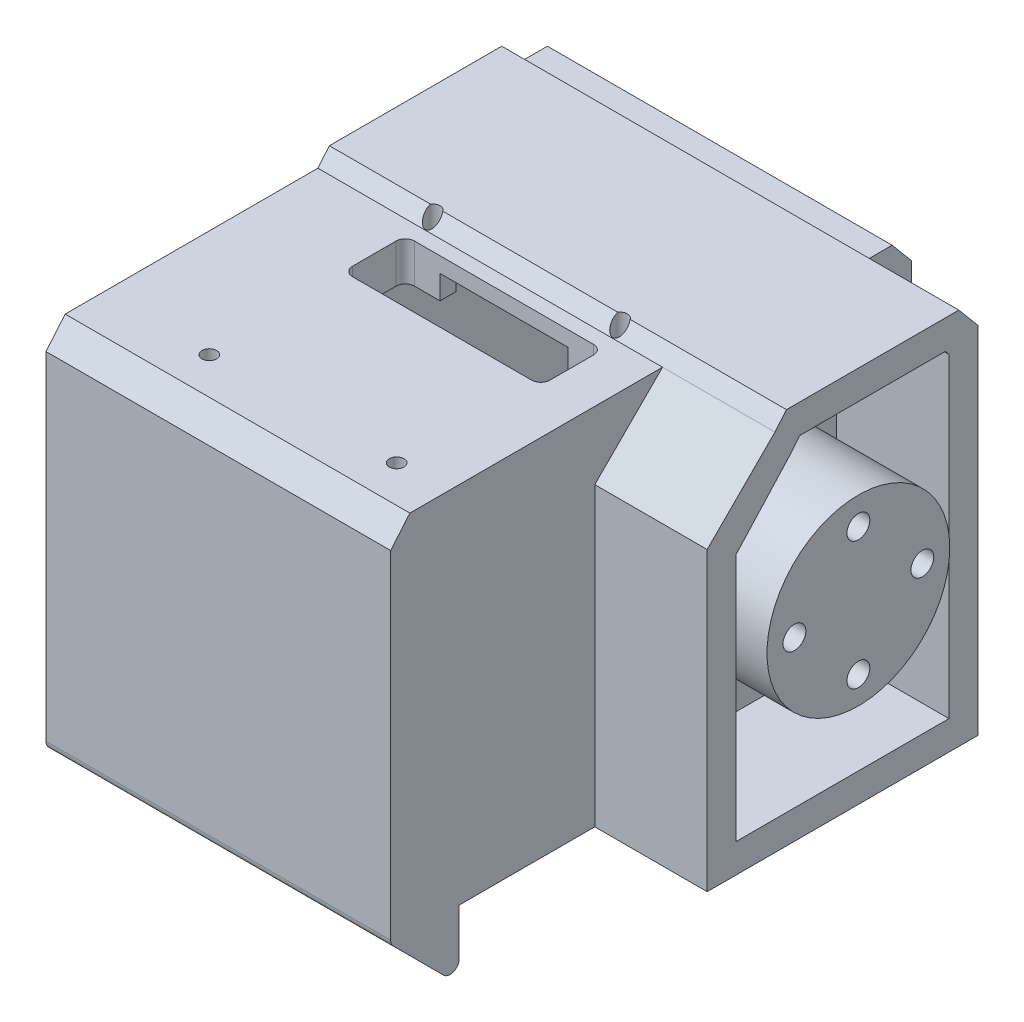
SolidWorks part; units mm, degrees
material "PLA"
ref_plane "Front Plane" through (0, 0, 0) normal (0, 0, 1) x (1, 0, 0)
ref_plane "Top Plane" through (0, 0, 0) normal (0, 1, 0) x (1, 0, 0)
ref_plane "Right Plane" through (0, 0, 0) normal (1, 0, 0) x (0, 0, -1)
sketch "Sketch1" plane through (0, 0, 0) normal (1, 0, 0) x (0, 0, -1)
  line L0 (-25.985, 0) -> (25.985, 0) construction
  line L1 (0, 21.625) -> (0, -21.625) construction
  line L7 (-25.985, -21.625) -> (25.985, -21.625)
  line L8 (-25.985, -21.625) -> (-25.985, 21.625)
  line L9 (-25.985, 21.625) -> (25.985, 21.625)
  line L10 (25.985, -21.625) -> (25.985, 21.625)
  point P5 (0, 0)
  dimension "D1" = 51.97
  dimension "D2" = 43.25
extrude "Boss-Extrude1" add sketch "Sketch1" along normal blind 3.175
sketch "Sketch2" plane through (3.175, 0, 0) normal (1, 0, 0) x (0, 0, -1)
  line L8 (-22.81, 18.45) -> (-22.81, -18.45)
  line L9 (-22.81, -18.45) -> (22.81, -18.45)
  line L10 (22.81, -18.45) -> (22.81, 18.45)
  line L11 (22.81, 18.45) -> (-22.81, 18.45)
  line L12 (-22.81, 18.45) -> (-22.81, -18.45)
  line L13 (-22.81, -18.45) -> (22.81, -18.45)
  line L14 (22.81, -18.45) -> (22.81, 18.45)
  line L15 (22.81, 18.45) -> (-22.81, 18.45)
  line L16 (-25.985, 21.625) -> (-25.985, -21.625)
  line L17 (-25.985, -21.625) -> (25.985, -21.625)
  line L18 (25.985, -21.625) -> (25.985, 21.625)
  line L19 (25.985, 21.625) -> (-25.985, 21.625)
  line L20 (-25.985, 21.625) -> (-25.985, -21.625)
  line L21 (-25.985, -21.625) -> (25.985, -21.625)
  line L22 (25.985, -21.625) -> (25.985, 21.625)
  line L23 (25.985, 21.625) -> (-25.985, 21.625)
  dimension "D1" = 3.175
  dimension "D2" = 0
extrude "Boss-Extrude2" add sketch "Sketch2" along normal blind 25.12
sketch "Sketch5" plane through (0, 18.45, 0) normal (0, -1, 0) x (1, 0, 0)
  line L0 (6.0285, -6.9385) -> (3.175, -6.9385)
  line L1 (25.4415, -6.9385) -> (28.295, -6.9385)
  line L4 (3.175, 22.81) -> (3.175, -22.81)
  line L5 (3.175, -22.81) -> (28.295, -22.81)
  line L6 (28.295, -22.81) -> (28.295, 22.81)
  line L7 (28.295, 22.81) -> (3.175, 22.81)
  line L8 (3.175, 22.81) -> (3.175, -6.9385)
  line L10 (28.295, -6.9385) -> (28.295, 22.81)
  line L11 (28.295, 22.81) -> (3.175, 22.81)
  line L36 (26.535, -2.15) -> (22.735, -2.15)
  line L37 (26.535, 4.625) -> (26.535, -2.15)
  line L38 (25.038, 4.625) -> (26.535, 4.625)
  line L39 (25.1773, 4.8479) -> (25.038, 4.625)
  line L40 (25.1773, 15.8031) -> (25.1773, 4.8479)
  line L41 (7.4927, 17.0031) -> (23.9773, 17.0031)
  line L42 (6.2927, 4.8479) -> (6.2927, 15.8031)
  line L43 (6.432, 4.625) -> (6.2927, 4.8479)
  line L44 (4.935, 4.625) -> (6.432, 4.625)
  line L45 (4.935, -2.15) -> (4.935, 4.625)
  line L46 (8.735, -2.15) -> (4.935, -2.15)
  line L47 (8.735, -3.9136) -> (8.735, -2.15)
  line L48 (4.375, -6.9385) -> (6.0285, -6.9385)
  line L49 (3.875, 20.2102) -> (3.875, -6.4385)
  line L50 (26.0951, 21.71) -> (5.3746, 21.71)
  line L51 (27.595, -6.4385) -> (27.595, 20.2105)
  line L52 (25.4415, -6.9385) -> (27.095, -6.9385)
  line L53 (22.735, -2.15) -> (22.735, -3.9136)
  line L54 (26.535, -2.15) -> (22.735, -2.15)
  line L55 (26.535, 4.625) -> (26.535, -2.15)
  line L56 (25.038, 4.625) -> (26.535, 4.625)
  line L57 (25.1773, 4.8479) -> (25.038, 4.625)
  line L58 (25.1773, 15.8031) -> (25.1773, 4.8479)
  line L59 (7.4927, 17.0031) -> (23.9773, 17.0031)
  line L60 (6.2927, 4.8479) -> (6.2927, 15.8031)
  line L61 (6.432, 4.625) -> (6.2927, 4.8479)
  line L62 (4.935, 4.625) -> (6.432, 4.625)
  line L63 (4.935, -2.15) -> (4.935, 4.625)
  line L64 (8.735, -2.15) -> (4.935, -2.15)
  line L65 (8.735, -3.9136) -> (8.735, -2.15)
  line L71 (22.735, -2.15) -> (22.735, -3.9136)
  arc A12 (25.1773, 15.8031) -> (23.9773, 17.0031) centre (23.9773, 15.8031) ccw
  arc A13 (7.4927, 17.0031) -> (6.2927, 15.8031) centre (7.4927, 15.8031) ccw
  arc A14 (8.735, -3.9136) -> (6.0285, -6.9385) centre (15.735, -12.9) ccw
  arc A15 (3.875, -6.4385) -> (4.375, -6.9385) centre (4.375, -6.4385) ccw
  arc A16 (27.095, -6.9385) -> (27.595, -6.4385) centre (27.095, -6.4385) ccw
  arc A17 (25.4415, -6.9385) -> (22.735, -3.9136) centre (15.735, -12.9) ccw
  arc A18 (25.1773, 15.8031) -> (23.9773, 17.0031) centre (23.9773, 15.8031) ccw
  arc A19 (7.4927, 17.0031) -> (6.2927, 15.8031) centre (7.4927, 15.8031) ccw
  arc A20 (8.735, -3.9136) -> (6.0285, -6.9385) centre (15.735, -12.9) ccw
  arc A23 (25.4415, -6.9385) -> (22.735, -3.9136) centre (15.735, -12.9) ccw
  circle A68 centre (5.485, -4.6) radius 0.8
  circle A69 centre (5.485, 19.85) radius 0.8
  circle A70 centre (25.985, 19.85) radius 0.8
  circle A71 centre (25.985, -4.6) radius 0.8
  spline S4 degree 3 poles (199.8506, -959.1962) (36.727, -55.2614) (14.0519, 23.473) (4.9866, 21.6619) (4.8913, 21.6332) (4.7098, 21.558) (4.6238, 21.5118) (4.4608, 21.403) (4.3836, 21.3399) (4.1763, 21.1325) (4.0645, 20.9654) (1.0086, 13.5957) (53.0588, -19.6485) (521.6785, 875.7094) knots -11.579327 -11.579327 -11.579327 -11.579327 0.125 0.125 0.25 0.25 0.375 0.375 0.5 0.5 0.75 0.75 10.719736 10.719736 10.719736 10.719736 only from (5.3746, 21.71) to (3.875, 20.2102)
  spline S5 degree 3 poles (-953.307, -174.2909) (-49.38, -11.1451) (29.3583, 11.5329) (27.5469, 20.5985) (27.5181, 20.6937) (27.443, 20.8752) (27.3968, 20.9612) (27.288, 21.1242) (27.2248, 21.2014) (27.0175, 21.4088) (26.8503, 21.5206) (19.4805, 24.5762) (-13.7629, -27.4761) (881.6326, -496.0119) knots -11.579675 -11.579675 -11.579675 -11.579675 0.125 0.125 0.25 0.25 0.375 0.375 0.5 0.5 0.75 0.75 10.719832 10.719832 10.719832 10.719832 only from (27.595, 20.2105) to (26.0951, 21.71)
  dimension "D3" = 1.6
  dimension "D1" = 0.2
  dimension "D2" = 0
extrude "Boss-Extrude4" add sketch "Sketch5" along normal blind 2.6
sketch "Sketch6" plane through (0, 18.45, 0) normal (0, -1, 0) x (1, 0, 0)
  line L1 (4.935, 4.625) -> (26.535, 4.625)
  line L2 (4.935, 4.625) -> (4.935, -2.15)
  line L3 (4.935, -2.15) -> (26.535, -2.15)
  line L4 (26.535, 4.625) -> (26.535, -2.15)
  line L18 (6.0285, -6.9385) -> (3.175, -6.9385)
  line L19 (3.175, -6.9385) -> (3.175, -22.81)
  line L20 (3.175, -22.81) -> (28.295, -22.81)
  line L21 (28.295, -22.81) -> (28.295, -6.9385)
  line L22 (28.295, -6.9385) -> (25.4415, -6.9385)
  line L23 (22.735, -3.9136) -> (22.735, -2.15)
  line L24 (22.735, -2.15) -> (26.535, -2.15)
  line L25 (26.535, -2.15) -> (26.535, 4.625)
  line L26 (26.535, 4.625) -> (25.038, 4.625)
  line L27 (25.038, 4.625) -> (25.1773, 4.8479)
  line L28 (25.1773, 4.8479) -> (25.1773, 15.8031)
  line L29 (23.9773, 17.0031) -> (7.4927, 17.0031)
  line L30 (6.2927, 15.8031) -> (6.2927, 4.8479)
  line L31 (6.2927, 4.8479) -> (6.432, 4.625)
  line L32 (6.432, 4.625) -> (4.935, 4.625)
  line L33 (4.935, 4.625) -> (4.935, -2.15)
  line L34 (4.935, -2.15) -> (8.735, -2.15)
  line L35 (8.735, -2.15) -> (8.735, -3.9136)
  line L42 (22.735, -2.15) -> (26.535, -2.15)
  line L43 (26.535, -2.15) -> (26.535, 4.625)
  line L44 (26.535, 4.625) -> (25.038, 4.625)
  line L50 (6.432, 4.625) -> (4.935, 4.625)
  line L51 (4.935, 4.625) -> (4.935, -2.15)
  line L52 (4.935, -2.15) -> (8.735, -2.15)
  arc A4 (8.735, -3.9136) -> (6.0285, -6.9385) centre (15.735, -12.9) ccw
  arc A5 (25.4415, -6.9385) -> (22.735, -3.9136) centre (15.735, -12.9) ccw
  arc A6 (25.1773, 15.8031) -> (23.9773, 17.0031) centre (23.9773, 15.8031) ccw
  arc A7 (7.4927, 17.0031) -> (6.2927, 15.8031) centre (7.4927, 15.8031) ccw
  line M35 (22.735, -2.15) -> (26.535, -2.15)
  line M36 (26.535, -2.15) -> (26.535, 4.625)
  line M37 (26.535, 4.625) -> (25.038, 4.625)
  line M45 (6.432, 4.625) -> (4.935, 4.625)
  line M46 (4.935, 4.625) -> (4.935, -2.15)
  line M47 (4.935, -2.15) -> (8.735, -2.15)
  dimension "D1" = 0
extrude "Cut-Extrude2" cut sketch "Sketch6" against normal through all contours L3 L1 M47 M35 M36 M37 M45 M46 region at (15.735, 18.45, 1.2375)
fillet "Fillet4" radius 1 4 edges at (26.535, 18.7375, -2.15) (26.535, 18.7375, 4.625) (4.935, 18.7375, -2.15) (4.935, 18.7375, 4.625)
sketch "Sketch7" plane through (0, 21.625, 0) normal (0, 1, 0) x (1, 0, 0)
  line L0 (28.295, 25.985) -> (28.295, -25.985) construction
  line L1 (0, -25.985) -> (28.295, -25.985)
  line L2 (0, -25.985) -> (0, 3.765)
  line L3 (0, 3.765) -> (28.295, 3.765)
  line L4 (28.295, -25.985) -> (28.295, 3.765)
  line M5 (25.535, -4.625) -> (5.935, -4.625)
  arc M6 (5.935, -4.625) -> (4.935, -3.625) centre (5.935, -3.625) cw
  line M7 (4.935, -3.625) -> (4.935, 1.15)
  arc M8 (4.935, 1.15) -> (5.935, 2.15) centre (5.935, 1.15) cw
  line M9 (5.935, 2.15) -> (25.535, 2.15)
  arc M10 (25.535, 2.15) -> (26.535, 1.15) centre (25.535, 1.15) cw
  line M11 (26.535, 1.15) -> (26.535, -3.625)
  arc M12 (26.535, -3.625) -> (25.535, -4.625) centre (25.535, -3.625) cw
  line M13 (0, 25.985) -> (0, -25.985)
  line M14 (0, -25.985) -> (28.295, -25.985)
  line M15 (28.295, -25.985) -> (28.295, 25.985)
  dimension "D1" = 29.75
extrude "Cut-Extrude3" cut sketch "Sketch7" against normal blind 1.5 contours L3 M13 M14 M15 M12 M5 M6 M7 M8 M9 M10 M11 region at (13.8158, 21.625, 13.1727)
chamfer "Chamfer3" distance 1.5 angle 40 1 edges at (14.1475, 21.625, -3.765) first distance on face at (14.1475, 20.875, -3.765)
chamfer "Chamfer4" distance 2.5 angle 40 1 edges at (14.1475, 20.125, 25.985) first distance on face at (14.1475, -0.75, 25.985)
chamfer "Chamfer5" distance 2.5 angle 40 1 edges at (14.1475, 21.625, -25.985) first distance on face at (14.1475, 0, -25.985)
sketch "Sketch8" plane through (0, -18.45, 0) normal (0, 1, 0) x (1, 0, 0)
  line L1 (8.535, 2.2774) -> (8.535, -21.2062)
  line L6 (22.935, -21.2062) -> (22.935, 2.2774)
  line L8 (5.6661, 6.9407) -> (3.175, 6.9407)
  line L11 (25.803, 6.9392) -> (28.295, 6.9392)
  line L16 (8.8158, -21.9777) -> (8.8158, -22.81)
  line L18 (22.6542, -21.9776) -> (22.6542, -22.81)
  line L19 (3.175, 22.81) -> (3.175, -22.81)
  line L20 (3.175, -22.81) -> (28.295, -22.81)
  line L21 (28.295, -22.81) -> (28.295, 22.81)
  line L22 (28.295, 22.81) -> (3.175, 22.81)
  line L23 (3.175, 6.9407) -> (3.175, -22.81)
  line L24 (3.175, -22.81) -> (8.8158, -22.81)
  line L25 (28.295, -22.81) -> (28.295, 6.9392)
  line L27 (22.6542, -22.81) -> (28.295, -22.81)
  arc A6 (5.6661, 6.9407) -> (9.0755, 3.2799) centre (15.735, 12.9) ccw
  arc A9 (9.0755, 3.2799) -> (8.535, 2.2774) centre (9.735, 2.2774) ccw
  arc A20 (8.535, -21.2062) -> (8.8158, -21.9777) centre (9.735, -21.2062) ccw
  arc A23 (22.6542, -21.9776) -> (22.935, -21.2062) centre (21.735, -21.2062) ccw
  arc A28 (22.935, 2.2774) -> (22.3945, 3.2799) centre (21.735, 2.2774) ccw
  arc A35 (22.3945, 3.2799) -> (25.803, 6.9392) centre (15.735, 12.9) ccw
  circle A56 centre (25.985, -16.1) radius 0.8
  circle A57 centre (5.485, 4.6) radius 0.8
  circle A58 centre (25.985, 4.6) radius 0.8
  circle A59 centre (5.485, -16.1) radius 0.8
  spline S5 degree 3 poles (5.6659, 6.9385) (5.666, 6.9385) (5.6664, 6.9383) (5.6671, 6.938) (5.6678, 6.9375) (5.6681, 6.9373) (5.6683, 6.9372) knots 0.329528 0.329528 0.329528 0.329528 0.414347 0.499166 0.583985 0.668804 0.668804 0.668804 0.668804
  line M1 (3.175, 22.81) -> (3.175, -22.81)
  line M2 (3.175, -22.81) -> (28.295, -22.81)
  line M3 (28.295, -22.81) -> (28.295, 22.81)
  dimension "D1" = 1.6
  dimension "D2" = 1.6
  dimension "D3" = 1.6
  dimension "D4" = 1.6
  dimension "D5" = 0
extrude "Boss-Extrude5" add sketch "Sketch8" along normal blind 1.9 contours A20 L1 A9 A6 L8 L16 A59 A57 M1 M2 | A35 A28 L6 A23 L18 L11 A58 A56 M2 M3 region at (5.8173, -18.45, 8.4819) region at (25.6526, -18.45, 8.4823)
sketch "Sketch9" plane through (0, 18.45, 0) normal (0, -1, 0) x (1, 0, 0)
  circle A0 centre (5.485, -4.6) radius 0.8 construction
  circle A1 centre (25.985, -4.6) radius 0.8 construction
  circle A2 centre (25.985, 19.85) radius 0.8 construction
  circle A3 centre (5.485, 19.85) radius 0.8 construction
  circle A4 centre (5.485, -4.6) radius 0.8
  circle A5 centre (25.985, -4.6) radius 0.8
  circle A6 centre (25.985, 19.85) radius 0.8
  circle A7 centre (5.485, 19.85) radius 0.8
extrude "Cut-Extrude4" cut sketch "Sketch9" against normal through all
sketch "Sketch10" plane through (0, -21.625, 0) normal (0, -1, 0) x (1, 0, 0)
  line L0 (28.295, 25.985) -> (28.295, -25.985) construction
  line L1 (0, 25.985) -> (28.295, 25.985)
  line L2 (0, 25.985) -> (0, -6.935)
  line L3 (0, -6.935) -> (28.295, -6.935)
  line L4 (28.295, 25.985) -> (28.295, -6.935)
  dimension "D1" = 32.92
extrude "Cut-Extrude5" cut sketch "Sketch10" against normal blind 1.9
chamfer "Chamfer6" distance 1.9 angle 40 1 edges at (14.1475, -19.725, -6.935) first distance on face at (14.1475, -20.675, -6.935)
sketch "Sketch11" plane through (0, -18.45, 0) normal (0, 1, 0) x (1, 0, 0)
  line L10 (3.175, 22.81) -> (3.175, 6.9407)
  line L11 (3.175, 6.9407) -> (5.6661, 6.9407)
  line L12 (8.535, 2.2774) -> (8.535, -21.2062)
  line L13 (8.8158, -21.9777) -> (8.8158, -22.81)
  line L14 (8.8158, -22.81) -> (22.6542, -22.81)
  line L15 (22.6542, -22.81) -> (22.6542, -21.9776)
  line L16 (22.935, -21.2062) -> (22.935, 2.2774)
  line L17 (25.803, 6.9392) -> (28.295, 6.9392)
  line L18 (28.295, 6.9392) -> (28.295, 22.81)
  line L19 (28.295, 22.81) -> (3.175, 22.81)
  line L20 (3.175, 22.81) -> (3.175, 6.9407)
  line L21 (3.175, 6.9407) -> (5.6661, 6.9407)
  line L27 (25.803, 6.9392) -> (28.295, 6.9392)
  line L28 (28.295, 6.9392) -> (28.295, 22.81)
  line L29 (28.295, 22.81) -> (3.175, 22.81)
  arc A0 (9.0755, 3.2799) -> (22.3945, 3.2799) centre (15.735, 9.9394) ccw
  arc A6 (5.6661, 6.9407) -> (9.0755, 3.2799) centre (15.735, 12.9) ccw
  arc A7 (9.0755, 3.2799) -> (8.535, 2.2774) centre (9.735, 2.2774) ccw
  arc A8 (8.535, -21.2062) -> (8.8158, -21.9777) centre (9.735, -21.2062) ccw
  arc A9 (22.6542, -21.9776) -> (22.935, -21.2062) centre (21.735, -21.2062) ccw
  arc A10 (22.935, 2.2774) -> (22.3945, 3.2799) centre (21.735, 2.2774) ccw
  arc A11 (22.3945, 3.2799) -> (25.803, 6.9392) centre (15.735, 12.9) ccw
  arc A12 (5.6661, 6.9407) -> (9.0755, 3.2799) centre (15.735, 12.9) ccw
  arc A17 (22.3945, 3.2799) -> (25.803, 6.9392) centre (15.735, 12.9) ccw
  dimension "D1" = 0
extrude "Cut-Extrude6" cut sketch "Sketch11" against normal through all
sketch "Sketch12" plane through (0, -18.45, 0) normal (0, 1, 0) x (1, 0, 0)
  circle A0 centre (25.985, 4.6) radius 0.8 construction
  circle A1 centre (25.985, -16.1) radius 0.8 construction
  circle A2 centre (5.485, -16.1) radius 0.8 construction
  circle A3 centre (5.485, 4.6) radius 0.8 construction
  circle A4 centre (25.985, 4.6) radius 0.8
  circle A5 centre (25.985, -16.1) radius 0.8
  circle A6 centre (5.485, -16.1) radius 0.8
  circle A7 centre (5.485, 4.6) radius 0.8
extrude "Cut-Extrude7" cut sketch "Sketch12" against normal through all
sketch "Sketch13" plane through (0, -21.625, 0) normal (0, -1, 0) x (1, 0, 0)
  line L0 (28.295, -5.3407) -> (28.295, 25.985) construction
  line L1 (0, -25.985) -> (28.295, -25.985)
  line L2 (0, -25.985) -> (0, 7.0246)
  line L3 (0, 7.0246) -> (28.295, 7.0246)
  line L4 (28.295, -25.985) -> (28.295, 7.0246)
extrude "Cut-Extrude8" cut sketch "Sketch13" against normal up to surface (1.9 mm away) up to face at (15.2058, -19.725, 0.7228)
sketch "Sketch14" plane through (28.295, 0, 0) normal (1, 0, 0) x (0, 0, -1)
  line L0 (6.9392, -16.55) -> (22.81, -16.55)
  line L1 (6.9392, -19.725) -> (22.81, -19.725)
  line L3 (6.9392, -16.55) -> (22.81, -16.55)
  line L5 (6.9392, -19.725) -> (22.81, -19.725)
  line L16 (-25.985, -19.725) -> (6.9392, -19.725)
  line L17 (6.9392, -19.725) -> (6.9392, -16.55)
  line L18 (6.9392, -16.55) -> (-22.81, -16.55)
  line L19 (-22.81, -16.55) -> (-22.81, 15.85)
  line L20 (-22.81, 15.85) -> (6.9385, 15.85)
  line L21 (6.9385, 15.85) -> (6.9385, 18.45)
  line L22 (6.9385, 18.45) -> (22.81, 18.45)
  line L23 (22.81, 18.45) -> (22.81, -19.725)
  line L24 (22.81, -19.725) -> (25.985, -19.725)
  line L25 (25.985, -19.725) -> (25.985, 19.125)
  line L26 (25.985, 19.125) -> (23.8873, 21.625)
  line L27 (23.8873, 21.625) -> (5.0236, 21.625)
  line L28 (5.0236, 21.625) -> (3.765, 20.125)
  line L29 (3.765, 20.125) -> (-23.8873, 20.125)
  line L30 (-23.8873, 20.125) -> (-25.985, 17.625)
  line L31 (-25.985, 17.625) -> (-25.985, -19.725)
  line L32 (-25.985, -19.725) -> (6.9392, -19.725)
  line L34 (6.9392, -16.55) -> (-22.81, -16.55)
  line L35 (-22.81, -16.55) -> (-22.81, 15.85)
  line L36 (-22.81, 15.85) -> (6.9385, 15.85)
  line L37 (6.9385, 15.85) -> (6.9385, 18.45)
  line L38 (6.9385, 18.45) -> (22.81, 18.45)
  line L39 (22.81, 18.45) -> (22.81, -16.55)
  line L40 (22.81, -19.725) -> (25.985, -19.725)
  line L41 (25.985, -19.725) -> (25.985, 19.125)
  line L42 (25.985, 19.125) -> (23.8873, 21.625)
  line L43 (23.8873, 21.625) -> (5.0236, 21.625)
  line L44 (5.0236, 21.625) -> (3.765, 20.125)
  line L45 (3.765, 20.125) -> (-23.8873, 20.125)
  line L46 (-23.8873, 20.125) -> (-25.985, 17.625)
  line L47 (-25.985, 17.625) -> (-25.985, -19.725)
  line M21 (-25.985, -19.725) -> (6.9392, -19.725)
  line M22 (6.9392, -19.725) -> (6.9392, -16.55)
  line M23 (6.9392, -16.55) -> (-22.81, -16.55)
  line M24 (-22.81, -16.55) -> (-22.81, 15.85)
  line M25 (-22.81, 15.85) -> (6.9385, 15.85)
  line M26 (6.9385, 15.85) -> (6.9385, 18.45)
  line M27 (6.9385, 18.45) -> (22.81, 18.45)
  line M28 (22.81, 18.45) -> (22.81, -19.725)
  line M29 (22.81, -19.725) -> (25.985, -19.725)
  line M30 (25.985, -19.725) -> (25.985, 19.125)
  line M31 (25.985, 19.125) -> (23.8873, 21.625)
  line M32 (23.8873, 21.625) -> (5.0236, 21.625)
  line M33 (5.0236, 21.625) -> (3.765, 20.125)
  line M34 (3.765, 20.125) -> (-23.8873, 20.125)
  line M35 (-23.8873, 20.125) -> (-25.985, 17.625)
  line M36 (-25.985, 17.625) -> (-25.985, -19.725)
  dimension "D1" = 0
extrude "Boss-Extrude6" add sketch "Sketch14" along normal blind 3.175 contours M36 M21 M22 M23 M24 M25 M26 M27 M28 M29 M30 M31 M32 M33 M34 M35 | L1 L0 M22 M28 | L40 L41 L42 L43 L44 L45 L46 L47 L32 L1 region at (28.295, -18.1375, -14.8746) region at (28.295, -18.1375, -6.275)
sketch "Sketch15" plane through (31.47, 0, 0) normal (1, 0, 0) x (0, 0, -1)
  line L0 (25.985, 0) -> (12.495, 0) construction
  line L1 (25.985, -19.725) -> (25.985, 19.125) construction
  circle A0 centre (12.495, 0) radius 10
  circle A1 centre (12.495, 0) radius 7 construction
  circle A2 centre (12.495, 7) radius 1.25
  circle A3 centre (19.495, 0) radius 1.25
  circle A4 centre (5.495, 0) radius 1.25
  circle A5 centre (12.495, -7) radius 1.25
  dimension "D2" = 20
  dimension "D3" = 14
  dimension "D4" = 2.5
  dimension "D1" = 13.49
extrude "Boss-Extrude7" add sketch "Sketch15" along normal blind 12.7
sketch "Sketch16" plane through (31.47, 0, 0) normal (1, 0, 0) x (0, 0, -1)
  circle A0 centre (19.495, 0) radius 1.25 construction
  circle A1 centre (12.495, -7) radius 1.25 construction
  circle A2 centre (5.495, 0) radius 1.25 construction
  circle A3 centre (12.495, 7) radius 1.25 construction
  circle A4 centre (19.495, 0) radius 1.25
  circle A5 centre (12.495, -7) radius 1.25
  circle A6 centre (5.495, 0) radius 1.25
  circle A7 centre (12.495, 7) radius 1.25
extrude "Cut-Extrude9" cut sketch "Sketch16" against normal up to surface (3.175 mm away) up to face at (28.295, -0.4938, -3.4694)
sketch "Sketch17" plane through (31.47, 0, 0) normal (1, 0, 0) x (0, 0, -1)
  line L1 (-0.4777, -16.55) -> (22.81, -16.55)
  line L2 (22.81, -16.55) -> (22.81, 17.9694)
  line L3 (22.81, 17.9694) -> (22.4067, 18.45)
  line L4 (22.4067, 18.45) -> (6.5042, 18.45)
  line L5 (6.5042, 18.45) -> (5.2455, 16.95)
  line L8 (-25.985, 17.625) -> (-25.985, -19.725)
  line L9 (-25.985, -19.725) -> (25.985, -19.725)
  line L10 (25.985, -19.725) -> (25.985, 19.125)
  line L11 (25.985, 19.125) -> (23.8873, 21.625)
  line L12 (23.8873, 21.625) -> (5.0236, 21.625)
  line L13 (5.0236, 21.625) -> (3.765, 20.125)
  line L14 (3.765, 20.125) -> (-23.8873, 20.125)
  line L15 (-23.8873, 20.125) -> (-25.985, 17.625)
  line L18 (25.985, -19.725) -> (25.985, 19.125)
  line L19 (25.985, 19.125) -> (23.8873, 21.625)
  line L20 (23.8873, 21.625) -> (5.0236, 21.625)
  line L21 (5.0236, 21.625) -> (3.765, 20.125)
  line L24 (5.2455, 16.95) -> (-0.4777, 10.6655)
  line L25 (-0.4777, 10.6655) -> (-0.4777, -16.55)
  line L26 (-3.6527, -16.55) -> (-3.6527, -19.725)
  line L27 (-3.6527, 11.6724) -> (-3.6527, -16.55)
  line L28 (3.765, 20.125) -> (-3.6527, 12.7073)
  line L29 (5.2455, 16.95) -> (-22.4067, 16.95) construction
  line L30 (-3.6527, 12.7073) -> (-3.6527, 11.6724)
  line L31 (-22.81, -16.55) -> (22.81, -16.55) construction
  line L32 (3.765, 20.125) -> (-23.8873, 20.125) construction
  line L33 (-23.8873, 20.125) -> (-25.985, 17.625) construction
  line L34 (-25.985, 17.625) -> (-25.985, -19.725) construction
  line L35 (-22.81, 16.4694) -> (-22.81, -16.55) construction
  line L36 (-22.4067, 16.95) -> (-22.81, 16.4694) construction
  line L37 (-25.985, -19.725) -> (25.985, -19.725) construction
  line L38 (-25.985, -19.725) -> (25.985, -19.725) construction
  line L39 (-3.6527, -19.725) -> (25.985, -19.725)
  dimension "D3" = 8.5
  dimension "D4" = 3.175
  dimension "D1" = 0
  dimension "D2" = 3.175
extrude "Boss-Extrude8" add sketch "Sketch17" along normal blind 12.3
sketch "Sketch18" plane through (0, 0, 0) normal (-1, 0, 0) x (0, 0, 1)
  line L8 (-25.985, 19.125) -> (-25.985, -19.725)
  line L9 (-25.985, -19.725) -> (25.985, -19.725)
  line L10 (25.985, -19.725) -> (25.985, 17.625)
  line L11 (25.985, 17.625) -> (23.8873, 20.125)
  line L12 (23.8873, 20.125) -> (-3.765, 20.125)
  line L13 (-3.765, 20.125) -> (-5.0236, 21.625)
  line L14 (-5.0236, 21.625) -> (-23.8873, 21.625)
  line L15 (-23.8873, 21.625) -> (-25.985, 19.125)
  line L16 (-25.985, 19.125) -> (-25.985, -19.725)
  line L17 (-25.985, -19.725) -> (25.985, -19.725)
  line L18 (25.985, -19.725) -> (25.985, 17.625)
  line L19 (25.985, 17.625) -> (23.8873, 20.125)
  line L20 (23.8873, 20.125) -> (-3.765, 20.125)
  line L21 (-3.765, 20.125) -> (-5.0236, 21.625)
  line L22 (-5.0236, 21.625) -> (-23.8873, 21.625)
  line L23 (-23.8873, 21.625) -> (-25.985, 19.125)
  dimension "D1" = 0
extrude "Boss-Extrude9" add sketch "Sketch18" along normal blind 6.25
sketch "Sketch19" plane through (-6.25, 0, 0) normal (-1, 0, 0) x (0, 0, 1)
  line L0 (-25.985, 19.125) -> (-30.985, 19.125)
  line L1 (-30.985, 19.125) -> (-30.985, -19.725)
  line L2 (-30.985, -19.725) -> (-25.985, -19.725)
  line L3 (-25.985, -19.725) -> (-25.985, 19.125)
  dimension "D1" = 5
extrude "Boss-Extrude10" add sketch "Sketch19" against normal up to surface (37.72 mm away) up to face at (31.47, 5.1887, 13.2329)
chamfer "Chamfer7" distance 2.5 angle 40 1 edges at (12.61, 19.125, -30.985) first distance on face at (12.61, -0.3, -30.985)
sketch "Sketch20" plane through (-6.25, 0, 0) normal (-1, 0, 0) x (0, 0, 1)
  line L38 (-25.985, 14.125) -> (-25.985, -14.725)
  line L39 (-25.985, -14.725) -> (20.985, -14.725)
  line L40 (20.985, -14.725) -> (20.985, 15.125)
  line L41 (20.985, 15.125) -> (-6.0965, 15.125)
  line L42 (-6.0965, 15.125) -> (-7.3552, 16.625)
  line L43 (-7.3552, 16.625) -> (-21.5557, 16.625)
  line L44 (-21.5557, 16.625) -> (-23.6535, 14.125)
  line L45 (-23.6535, 14.125) -> (-25.985, 14.125)
  line L46 (-25.985, 14.125) -> (-25.985, -12.225)
  line L47 (-23.485, -14.725) -> (18.485, -14.725)
  line L48 (20.985, -12.225) -> (20.985, 12.625)
  line L49 (18.485, 15.125) -> (-6.0965, 15.125)
  line L50 (-6.0965, 15.125) -> (-7.3552, 16.625)
  line L51 (-7.3552, 16.625) -> (-21.5557, 16.625)
  line L52 (-21.5557, 16.625) -> (-23.6535, 14.125)
  line L53 (-23.6535, 14.125) -> (-25.985, 14.125)
  arc A8 (-25.985, -12.225) -> (-23.485, -14.725) centre (-23.485, -12.225) ccw
  arc A9 (18.485, -14.725) -> (20.985, -12.225) centre (18.485, -12.225) ccw
  arc A10 (20.985, 12.625) -> (18.485, 15.125) centre (18.485, 12.625) ccw
  dimension "D2" = 2.5
  dimension "D1" = 5
extrude "Boss-Extrude11" add sketch "Sketch20" along normal blind 1
chamfer "Chamfer8" distance 1 angle 40 11 edges at (-7.25, 0.95, -25.985) (-7.25, 14.125, -24.8192) (-7.25, 15.375, -22.6046) (-7.25, 16.625, -14.4555) (-7.25, 15.875, -6.7259) (-7.25, 15.125, 6.1942) (-7.25, 14.3928, 20.2528) (-7.25, 0.2, 20.985) (-7.25, -13.9928, 20.2528) (-7.25, -14.725, -2.5) (-7.25, -13.9928, -25.2528) first distance on face at (-6.75, 0.95, -25.985) first distance on face at (-6.75, 14.125, -24.8192) first distance on face at (-6.75, 15.375, -22.6046) first distance on face at (-6.75, 16.625, -14.4555) first distance on face at (-6.75, 15.875, -6.7259) first distance on face at (-6.75, 15.125, 6.1942) first distance on face at (-6.75, 14.1339, 19.9939) first distance on face at (-6.75, 0.2, 20.985) first distance on face at (-6.75, -13.7339, 19.9939) first distance on face at (-6.75, -14.725, -2.5) first distance on face at (-6.75, -13.7339, -24.9939)
sketch "Sketch21" plane through (0, -16.55, 0) normal (0, 1, 0) x (1, 0, 0)
  line L0 (3.175, -7.9346) -> (28.295, -7.9354)
  line L5 (5.6661, 6.9407) -> (3.175, 6.9407)
  line L6 (3.175, 6.9407) -> (3.175, -22.81)
  line L7 (3.175, -22.81) -> (8.8158, -22.81)
  line L8 (8.8158, -22.81) -> (8.8158, -21.9777)
  line L9 (8.535, -21.2062) -> (8.535, 2.2774)
  line L10 (5.6661, 6.9407) -> (3.175, 6.9407)
  line L11 (3.175, 6.9407) -> (3.175, -7.9346)
  line L15 (22.935, 2.2774) -> (22.935, -21.2062)
  line L16 (22.6542, -21.9776) -> (22.6542, -22.81)
  line L17 (22.6542, -22.81) -> (28.295, -22.81)
  line L18 (28.295, -22.81) -> (28.295, 6.9392)
  line L19 (28.295, 6.9392) -> (25.803, 6.9392)
  line L23 (28.295, -7.9354) -> (28.295, 6.9392)
  line L24 (28.295, 6.9392) -> (25.803, 6.9392)
  line L25 (8.535, 2.2774) -> (8.535, -21.2062)
  line L26 (8.8158, -21.9777) -> (8.8158, -22.81)
  line L27 (8.8158, -22.81) -> (22.6542, -22.81)
  line L28 (22.6542, -22.81) -> (22.6542, -21.9776)
  line L29 (22.935, -21.2062) -> (22.935, 2.2774)
  arc A3 (5.6661, 6.9407) -> (9.0755, 3.2799) centre (15.735, 12.9) ccw
  arc A4 (8.535, -21.2062) -> (8.8158, -21.9777) centre (9.735, -21.2062) ccw
  arc A5 (9.0755, 3.2799) -> (8.535, 2.2774) centre (9.735, 2.2774) ccw
  arc A6 (5.6661, 6.9407) -> (9.0755, 3.2799) centre (15.735, 12.9) ccw
  arc A9 (22.3945, 3.2799) -> (25.803, 6.9392) centre (15.735, 12.9) ccw
  arc A10 (22.935, 2.2774) -> (22.3945, 3.2799) centre (21.735, 2.2774) ccw
  arc A11 (22.6542, -21.9776) -> (22.935, -21.2062) centre (21.735, -21.2062) ccw
  arc A12 (22.3945, 3.2799) -> (25.803, 6.9392) centre (15.735, 12.9) ccw
  arc A17 (9.0755, 3.2799) -> (22.3945, 3.2799) centre (15.735, 9.9394) ccw
  arc A18 (9.0755, 3.2799) -> (8.535, 2.2774) centre (9.735, 2.2774) ccw
  arc A19 (8.535, -21.2062) -> (8.8158, -21.9777) centre (9.735, -21.2062) ccw
  arc A20 (22.6542, -21.9776) -> (22.935, -21.2062) centre (21.735, -21.2062) ccw
  arc A21 (22.935, 2.2774) -> (22.3945, 3.2799) centre (21.735, 2.2774) ccw
  arc A22 (9.0755, 3.2799) -> (22.3945, 3.2799) centre (15.735, 9.9394) ccw
  dimension "D1" = 0
  dimension "D2" = 0
  dimension "D3" = 0
extrude "Cut-Extrude10" cut sketch "Sketch21" against normal through all
chamfer "Chamfer9" distance 6.35 angle 45 1 edges at (15.735, -19.725, -22.81)
sketch "Sketch22" plane through (31.47, 0, 0) normal (1, 0, 0) x (0, 0, -1)
  line L0 (-25.985, -19.725) -> (-18.485, -27.225)
  line L1 (-18.485, -27.225) -> (-18.485, -19.725)
  line L2 (-25.985, -19.725) -> (-3.6527, -19.725) construction
  line L3 (-18.485, -19.725) -> (-25.985, -19.725)
  dimension "D1" = 45
  dimension "D2" = 7.5
extrude "Boss-Extrude12" add sketch "Sketch22" against normal up to surface (37.72 mm away) up to face at (-6.25, 11.655, -7.3661)
fillet "Fillet5" radius 1 2 edges at (12.61, -19.725, -30.985) (12.61, -19.725, 25.985)
fillet "Fillet6" radius 1 1 edges at (12.61, -27.225, 18.485)
